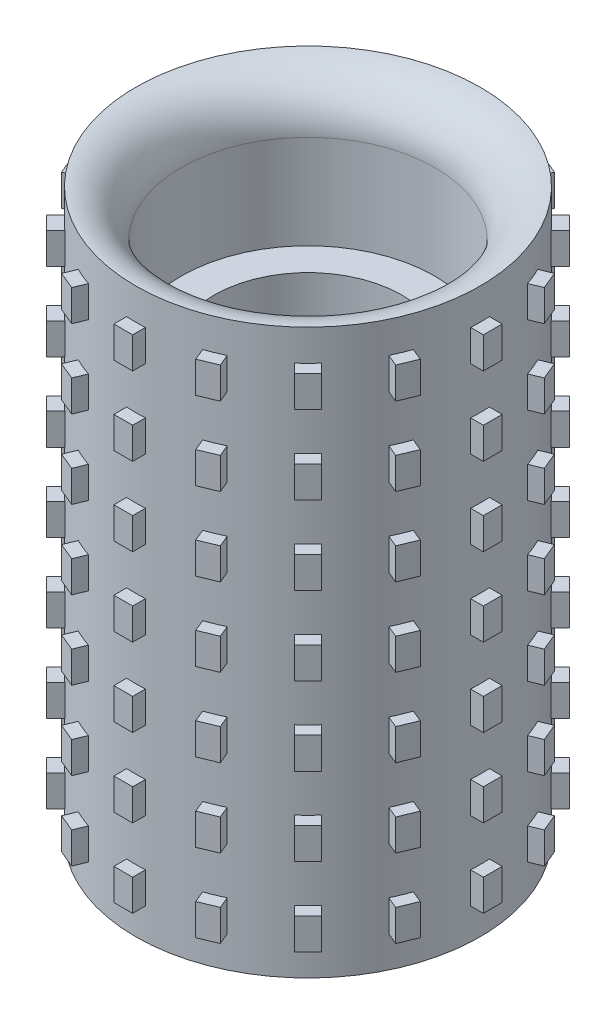
SolidWorks part; units mm, degrees
ref_plane "Front Plane" through (0, 0, 0) normal (0, 0, 1) x (1, 0, 0)
ref_plane "Top Plane" through (0, 0, 0) normal (0, 1, 0) x (1, 0, 0)
ref_plane "Right Plane" through (0, 0, 0) normal (1, 0, 0) x (0, 0, -1)
sketch "Sketch1" plane through (0, 0, 0) normal (0, 1, 0) x (1, 0, 0)
  circle A0 centre (0, 0) radius 11
  dimension "D1" = 22
extrude "Boss-Extrude1" add sketch "Sketch1" along normal mid plane 36
sketch "Sketch2" plane through (0, 0, 0) normal (0, 1, 0) x (1, 0, 0)
  circle A0 centre (0, 0) radius 6
  dimension "D1" = 12
extrude "Cut-Extrude1" cut sketch "Sketch2" against normal mid plane 18
sketch "Sketch3" plane through (0, -18, 0) normal (0, -1, 0) x (1, 0, 0)
  circle A0 centre (0, 0) radius 8.1
  dimension "D1" = 16.2
extrude "Cut-Extrude2" cut sketch "Sketch3" against normal up to surface (9 mm away) up to face at (0, -9, 6)
fillet "Fillet1" radius 3 1 edges at (0, -18, -8.1)
mirror "Mirror2" about plane through (0, 0, 0) normal (0, 1, 0) of "Cut-Extrude2", "Fillet1"
sketch "Sketch4" plane through (0, 0, 0) normal (0, 1, 0) x (1, 0, 0)
  line L0 (-0.6, 10.9836) -> (-0.6, 11.8)
  line L1 (-0.6, 11.8) -> (0.6, 11.8)
  line L2 (0.6, 11.8) -> (0.6, 10.9836)
  line L3 (0, -12.1) -> (0, 12.1) construction
  line L4 (3.6489, 10.3772) -> (3.9613, 11.1314)
  line L5 (3.9613, 11.1314) -> (5.07, 10.6722)
  line L6 (5.07, 10.6722) -> (4.7576, 9.9179)
  line L7 (7.3423, 8.1909) -> (7.9196, 8.7681)
  line L8 (7.9196, 8.7681) -> (8.7681, 7.9196)
  line L9 (8.7681, 7.9196) -> (8.1909, 7.3423)
  line L10 (9.9179, 4.7576) -> (10.6722, 5.07)
  line L11 (10.6722, 5.07) -> (11.1314, 3.9613)
  line L12 (11.1314, 3.9613) -> (10.3772, 3.6489)
  line L13 (10.9836, 0.6) -> (11.8, 0.6)
  line L14 (11.8, 0.6) -> (11.8, -0.6)
  line L15 (11.8, -0.6) -> (10.9836, -0.6)
  line L16 (10.3772, -3.6489) -> (11.1314, -3.9613)
  line L17 (11.1314, -3.9613) -> (10.6722, -5.07)
  line L18 (10.6722, -5.07) -> (9.9179, -4.7576)
  line L19 (8.1909, -7.3423) -> (8.7681, -7.9196)
  line L20 (8.7681, -7.9196) -> (7.9196, -8.7681)
  line L21 (7.9196, -8.7681) -> (7.3423, -8.1909)
  line L22 (4.7576, -9.9179) -> (5.07, -10.6722)
  line L23 (5.07, -10.6722) -> (3.9613, -11.1314)
  line L24 (3.9613, -11.1314) -> (3.6489, -10.3772)
  line L25 (0.6, -10.9836) -> (0.6, -11.8)
  line L26 (0.6, -11.8) -> (-0.6, -11.8)
  line L27 (-0.6, -11.8) -> (-0.6, -10.9836)
  line L28 (-3.6489, -10.3772) -> (-3.9613, -11.1314)
  line L29 (-3.9613, -11.1314) -> (-5.07, -10.6722)
  line L30 (-5.07, -10.6722) -> (-4.7576, -9.9179)
  line L31 (-7.3423, -8.1909) -> (-7.9196, -8.7681)
  line L32 (-7.9196, -8.7681) -> (-8.7681, -7.9196)
  line L33 (-8.7681, -7.9196) -> (-8.1909, -7.3423)
  line L34 (-9.9179, -4.7576) -> (-10.6722, -5.07)
  line L35 (-10.6722, -5.07) -> (-11.1314, -3.9613)
  line L36 (-11.1314, -3.9613) -> (-10.3772, -3.6489)
  line L37 (-10.9836, -0.6) -> (-11.8, -0.6)
  line L38 (-11.8, -0.6) -> (-11.8, 0.6)
  line L39 (-11.8, 0.6) -> (-10.9836, 0.6)
  line L40 (-10.3772, 3.6489) -> (-11.1314, 3.9613)
  line L41 (-11.1314, 3.9613) -> (-10.6722, 5.07)
  line L42 (-10.6722, 5.07) -> (-9.9179, 4.7576)
  line L43 (-8.1909, 7.3423) -> (-8.7681, 7.9196)
  line L44 (-8.7681, 7.9196) -> (-7.9196, 8.7681)
  line L45 (-7.9196, 8.7681) -> (-7.3423, 8.1909)
  line L46 (-4.7576, 9.9179) -> (-5.07, 10.6722)
  line L47 (-5.07, 10.6722) -> (-3.9613, 11.1314)
  line L48 (-3.9613, 11.1314) -> (-3.6489, 10.3772)
  circle A2 centre (0, 0) radius 11 construction
  arc A3 (0.6, 10.9836) -> (-0.6, 10.9836) centre (0, 0) ccw
  arc A4 (4.7576, 9.9179) -> (3.6489, 10.3772) centre (0, 0) ccw
  arc A5 (8.1909, 7.3423) -> (7.3423, 8.1909) centre (0, 0) ccw
  arc A6 (10.3772, 3.6489) -> (9.9179, 4.7576) centre (0, 0) ccw
  arc A7 (10.9836, -0.6) -> (10.9836, 0.6) centre (0, 0) ccw
  arc A8 (9.9179, -4.7576) -> (10.3772, -3.6489) centre (0, 0) ccw
  arc A9 (7.3423, -8.1909) -> (8.1909, -7.3423) centre (0, 0) ccw
  arc A10 (3.6489, -10.3772) -> (4.7576, -9.9179) centre (0, 0) ccw
  arc A11 (-0.6, -10.9836) -> (0.6, -10.9836) centre (0, 0) ccw
  arc A12 (-4.7576, -9.9179) -> (-3.6489, -10.3772) centre (0, 0) ccw
  arc A13 (-8.1909, -7.3423) -> (-7.3423, -8.1909) centre (0, 0) ccw
  arc A14 (-10.3772, -3.6489) -> (-9.9179, -4.7576) centre (0, 0) ccw
  arc A15 (-10.9836, 0.6) -> (-10.9836, -0.6) centre (0, 0) ccw
  arc A16 (-9.9179, 4.7576) -> (-10.3772, 3.6489) centre (0, 0) ccw
  arc A17 (-7.3423, 8.1909) -> (-8.1909, 7.3423) centre (0, 0) ccw
  arc A18 (-3.6489, 10.3772) -> (-4.7576, 9.9179) centre (0, 0) ccw
  point P4 (0, 11.8)
  dimension "D1" = 1.2
  dimension "D2" = 11.8
  dimension "D3" = 16
extrude "Boss-Extrude2" add sketch "Sketch4" along normal mid plane 2
pattern_linear "LPattern2" count 4 spacing 5 along (0, 1, 0) of "Boss-Extrude2"
mirror "Mirror3" about plane through (0, 0, 0) normal (0, 1, 0) of "LPattern2"
